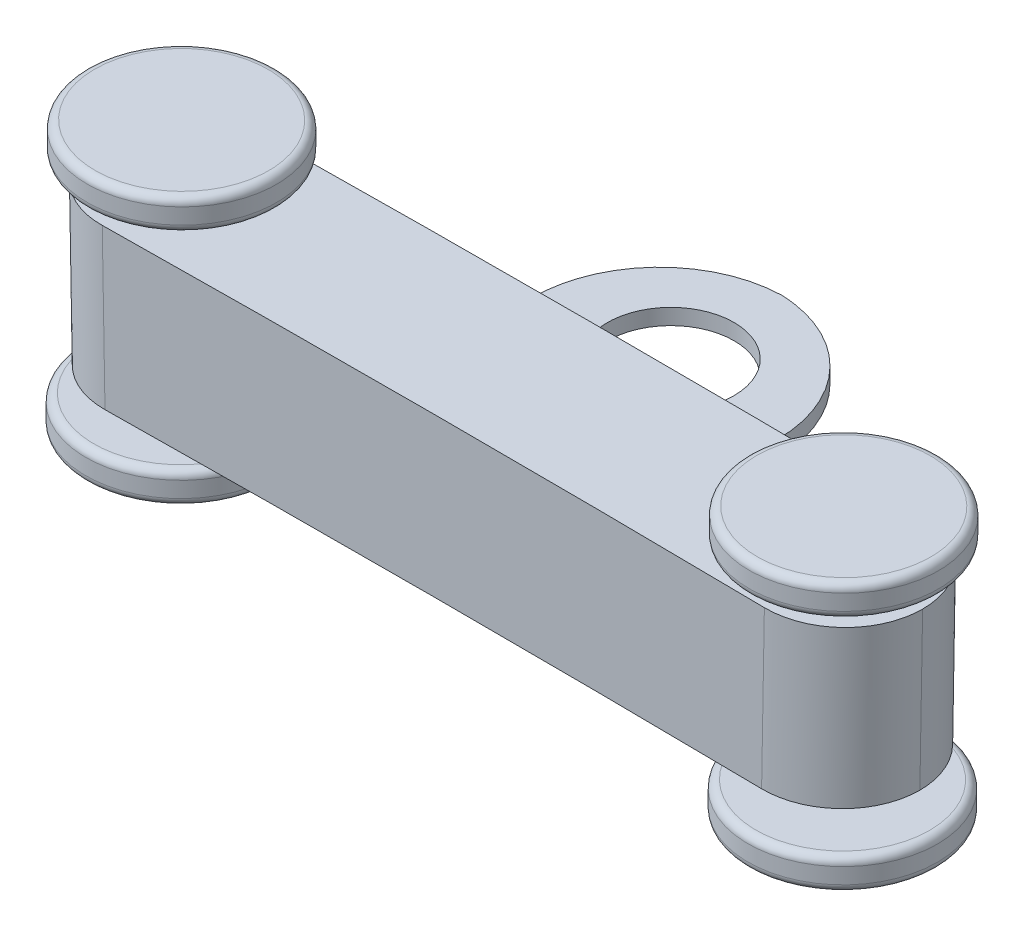
SolidWorks part; units mm, degrees
ref_plane "前视基准面" through (0, 0, 0) normal (0, 0, 1) x (1, 0, 0)
ref_plane "上视基准面" through (0, 0, 0) normal (0, 1, 0) x (1, 0, 0)
ref_plane "右视基准面" through (0, 0, 0) normal (1, 0, 0) x (0, 0, -1)
sketch "草图1" plane through (0, 0, 0) normal (0, 0, 1) x (1, 0, 0)
  line L0 (0, 1475) -> (0, 1485) construction
  line L5 (-25.7423, 1474.7754) -> (-25.9168, 1484.7738)
  line L6 (25.7423, 1474.7754) -> (25.9168, 1484.7738)
  arc A0 (25.8296, 1479.7746) -> (-25.8296, 1479.7746) centre (0, 0) ccw construction
  arc A1 (25.7423, 1474.7754) -> (-25.7423, 1474.7754) centre (0, 0) ccw
  arc A2 (25.9168, 1484.7738) -> (-25.9168, 1484.7738) centre (0, 0) ccw
  dimension "D1" = 2960
  dimension "D2" = 2950
  dimension "D3" = 2970
  dimension "D4" = 1
  dimension "D5" = 1
extrude "凸台-拉伸1" add sketch "草图1" along normal mid plane 10
fillet "圆角1" radius 5 4 edges at (25.8296, 1479.7746, 5) (25.8296, 1479.7746, -5) (-25.8296, 1479.7746, 5) (-25.8296, 1479.7746, -5)
sketch "草图3" plane through (0, 0, -5) normal (0, 0, -1) x (-1, 0, 0)
  line L0 (-7.7466, 1479.4797) -> (-7.7518, 1480.4797)
  line L1 (0, 1475) -> (0, 1485) construction
  line L2 (0, 1485) -> (0, 1475)
  line L3 (7.7466, 1479.4797) -> (7.7518, 1480.4797)
  arc A0 (7.7518, 1480.4797) -> (-7.7518, 1480.4797) centre (0, 0) ccw
  arc A1 (7.7466, 1479.4797) -> (-7.7466, 1479.4797) centre (0, 0) ccw
  dimension "D1" = 2961
  dimension "D2" = 2959
  dimension "D3" = 0.3
extrude "凸台-拉伸2" add sketch "草图3" along normal blind 12 contours A1 L2 A0 L0 | A1 L3 A0 L2 region at (3.8746, 1479.9933, -5) region at (-3.8746, 1479.9933, -5)
fillet "圆角2" radius 8 2 edges at (-7.7492, 1479.9797, -17) (7.7492, 1479.9797, -17)
sketch "草图4" plane through (0, 0, 0) normal (0, 1, 0) x (1, 0, 0)
  line L0 (-25.7423, 0) -> (25.7423, 0) construction
  line L3 (-20.9174, -5) -> (20.9174, -5)
  line L4 (20.9174, 5) -> (-20.9174, 5)
  line L5 (-20.9174, -5) -> (20.9174, -5)
  line L6 (20.9174, 5) -> (-20.9174, 5)
  circle A0 centre (0, 10) radius 4
  circle A1 centre (-20.9174, 0) radius 2
  circle A2 centre (20.9174, 0) radius 2
  spline S4 degree 3 poles (-588.3037, 2931.4937) (-114.1288, 363.486) (-13.5455, -11.9435) (22.0511, -4.8725) (22.2094, -4.8329) (22.5233, -4.7379) (22.6793, -4.6821) (23.1332, -4.4941) (23.4202, -4.3407) (23.9635, -3.9782) (24.2207, -3.7672) (24.6819, -3.3064) (24.8888, -3.0549) (25.2544, -2.5089) (25.4098, -2.2181) (25.6594, -1.6169) (25.7554, -1.3026) (35.5566, 47.7598) (-686.7716, 177.8556) (-2934.4746, 477.5123) knots -13.747899 -13.747899 -13.747899 -13.747899 0.125 0.125 0.1875 0.1875 0.25 0.25 0.375 0.375 0.5 0.5 0.625 0.625 0.75 0.75 0.875 0.875 19.739024 19.739024 19.739024 19.739024 only from (20.9174, -5) to (25.9168, 0)
  spline S5 degree 3 poles (-2910.6321, -609.1361) (-342.5489, -135.0521) (32.8597, -34.4682) (25.7893, 1.1338) (25.7498, 1.2921) (25.6547, 1.606) (25.599, 1.7621) (25.411, 2.216) (25.2576, 2.5031) (24.8952, 3.0464) (24.6842, 3.3037) (24.2234, 3.7649) (23.972, 3.9719) (23.4261, 4.3374) (23.1353, 4.4929) (22.5342, 4.7425) (22.2199, 4.8386) (-26.8365, 14.641) (-156.948, -707.7693) (-456.8971, -2955.3481) knots -13.748512 -13.748512 -13.748512 -13.748512 0.125 0.125 0.1875 0.1875 0.25 0.25 0.375 0.375 0.5 0.5 0.625 0.625 0.75 0.75 0.875 0.875 19.73873 19.73873 19.73873 19.73873 only from (25.9168, 0) to (20.9174, 5)
  spline S6 degree 3 poles (588.3037, -2931.4937) (114.1288, -363.486) (13.5455, 11.9435) (-22.0511, 4.8725) (-22.2094, 4.8329) (-22.5233, 4.7379) (-22.6793, 4.6821) (-23.1332, 4.4941) (-23.4202, 4.3407) (-23.9635, 3.9782) (-24.2207, 3.7672) (-24.6819, 3.3064) (-24.8888, 3.0549) (-25.2544, 2.5089) (-25.4098, 2.2181) (-25.6594, 1.6169) (-25.7554, 1.3026) (-35.5566, -47.7598) (686.7716, -177.8556) (2934.4746, -477.5123) knots -13.747899 -13.747899 -13.747899 -13.747899 0.125 0.125 0.1875 0.1875 0.25 0.25 0.375 0.375 0.5 0.5 0.625 0.625 0.75 0.75 0.875 0.875 19.739024 19.739024 19.739024 19.739024 only from (-20.9174, 5) to (-25.9168, 0)
  spline S7 degree 3 poles (2910.6321, 609.1361) (342.5489, 135.0521) (-32.8597, 34.4682) (-25.7893, -1.1338) (-25.7498, -1.2921) (-25.6547, -1.606) (-25.599, -1.7621) (-25.411, -2.216) (-25.2576, -2.5031) (-24.8952, -3.0464) (-24.6842, -3.3037) (-24.2234, -3.7649) (-23.972, -3.9719) (-23.4261, -4.3374) (-23.1353, -4.4929) (-22.5342, -4.7425) (-22.2199, -4.8386) (26.8365, -14.641) (156.948, 707.7693) (456.8971, 2955.3481) knots -13.748512 -13.748512 -13.748512 -13.748512 0.125 0.125 0.1875 0.1875 0.25 0.25 0.375 0.375 0.5 0.5 0.625 0.625 0.75 0.75 0.875 0.875 19.73873 19.73873 19.73873 19.73873 only from (-25.9168, 0) to (-20.9174, -5)
  spline S8 degree 3 poles (20.9174, -5) (21.2475, -5) (21.5721, -4.9676) (22.0511, -4.8725) (22.2094, -4.8329) (22.5233, -4.7379) (22.6793, -4.6821) (23.1332, -4.4941) (23.4202, -4.3407) (23.9635, -3.9782) (24.2207, -3.7672) (24.6819, -3.3064) (24.8888, -3.0549) (25.2544, -2.5089) (25.4098, -2.2181) (25.6594, -1.6169) (25.7554, -1.3026) (25.8844, -0.6567) (25.9168, -0.3301) (25.9168, 0) knots 0 0 0 0 0.125 0.125 0.1875 0.1875 0.25 0.25 0.375 0.375 0.5 0.5 0.625 0.625 0.75 0.75 0.875 0.875 1 1 1 1
  spline S9 degree 3 poles (25.9168, 0) (25.9168, 0.3301) (25.8845, 0.6548) (25.7893, 1.1338) (25.7498, 1.2921) (25.6547, 1.606) (25.599, 1.7621) (25.411, 2.216) (25.2576, 2.5031) (24.8952, 3.0464) (24.6842, 3.3037) (24.2234, 3.7649) (23.972, 3.9719) (23.4261, 4.3374) (23.1353, 4.4929) (22.5342, 4.7425) (22.2199, 4.8386) (21.574, 4.9676) (21.2475, 5) (20.9174, 5) knots 0 0 0 0 0.125 0.125 0.1875 0.1875 0.25 0.25 0.375 0.375 0.5 0.5 0.625 0.625 0.75 0.75 0.875 0.875 1 1 1 1
  spline S10 degree 3 poles (-20.9174, 5) (-21.2475, 5) (-21.5721, 4.9676) (-22.0511, 4.8725) (-22.2094, 4.8329) (-22.5233, 4.7379) (-22.6793, 4.6821) (-23.1332, 4.4941) (-23.4202, 4.3407) (-23.9635, 3.9782) (-24.2207, 3.7672) (-24.6819, 3.3064) (-24.8888, 3.0549) (-25.2544, 2.5089) (-25.4098, 2.2181) (-25.6594, 1.6169) (-25.7554, 1.3026) (-25.8844, 0.6567) (-25.9168, 0.3301) (-25.9168, 0) knots 0 0 0 0 0.125 0.125 0.1875 0.1875 0.25 0.25 0.375 0.375 0.5 0.5 0.625 0.625 0.75 0.75 0.875 0.875 1 1 1 1
  spline S11 degree 3 poles (-25.9168, 0) (-25.9168, -0.3301) (-25.8845, -0.6548) (-25.7893, -1.1338) (-25.7498, -1.2921) (-25.6547, -1.606) (-25.599, -1.7621) (-25.411, -2.216) (-25.2576, -2.5031) (-24.8952, -3.0464) (-24.6842, -3.3037) (-24.2234, -3.7649) (-23.972, -3.9719) (-23.4261, -4.3374) (-23.1353, -4.4929) (-22.5342, -4.7425) (-22.2199, -4.8386) (-21.574, -4.9676) (-21.2475, -5) (-20.9174, -5) knots 0 0 0 0 0.125 0.125 0.1875 0.1875 0.25 0.25 0.375 0.375 0.5 0.5 0.625 0.625 0.75 0.75 0.875 0.875 1 1 1 1
  dimension "D1" = 10
  dimension "D2" = 8
  dimension "D3" = 0
  dimension "D4" = 4
  dimension "D5" = 4
extrude "切除-拉伸1" cut sketch "草图4" along normal through all contours A0 region at (0, 0, -10)
ref_plane "基准面1" through (7.7754, 1484.9796, 0) normal (0.0052, 1, 0) x (1, -0.0052, 0)
sketch "草图5" plane through (7.7754, 1484.9796, 0) normal (0.0052, 1, 0) x (1, -0.0052, 0)
  line L0 (-33.4638, 0) -> (18.0201, 0) construction
  circle A0 centre (-28.6918, 0) radius 2
  circle A1 centre (13.1425, 0) radius 2
  dimension "D1" = 4
  dimension "D2" = 4
extrude "凸台-拉伸3" add sketch "草图5" along normal blind 1 and the other way blind 12
sketch "草图6" plane through (7.7806, 1485.9796, 0) normal (0.0052, 1, 0) x (1, -0.0052, 0)
  circle A0 centre (-28.6918, 0) radius 6
  circle A1 centre (13.1425, 0) radius 6
  dimension "D1" = 12
  dimension "D2" = 12
extrude "凸台-拉伸4" add sketch "草图6" along normal blind 2
sketch "草图7" plane through (7.7126, 1472.9798, 0) normal (-0.0052, -1, 0) x (1, -0.0052, 0)
  circle A0 centre (-28.6918, 0) radius 6
  circle A1 centre (13.1425, 0) radius 6
extrude "凸台-拉伸5" add sketch "草图7" along normal blind 2
fillet "圆角4" radius 0.5 13 edges at (-19.0233, 1474.8773, -0.46) (22.8113, 1474.8236, -0.46) (-14.9894, 1471.0986, 0) (-26.9002, 1488.1612, 0) (-18.9709, 1484.8788, 0.46) (-22.9107, 1486.1403, 0) (-26.9107, 1486.1613, 0) (-14.9789, 1473.0986, 0) (26.8444, 1470.8796, 0) (26.8548, 1472.8796, 0) (14.9231, 1485.9422, 0) (22.8637, 1484.824, 0.46) (14.9335, 1487.9422, 0)
